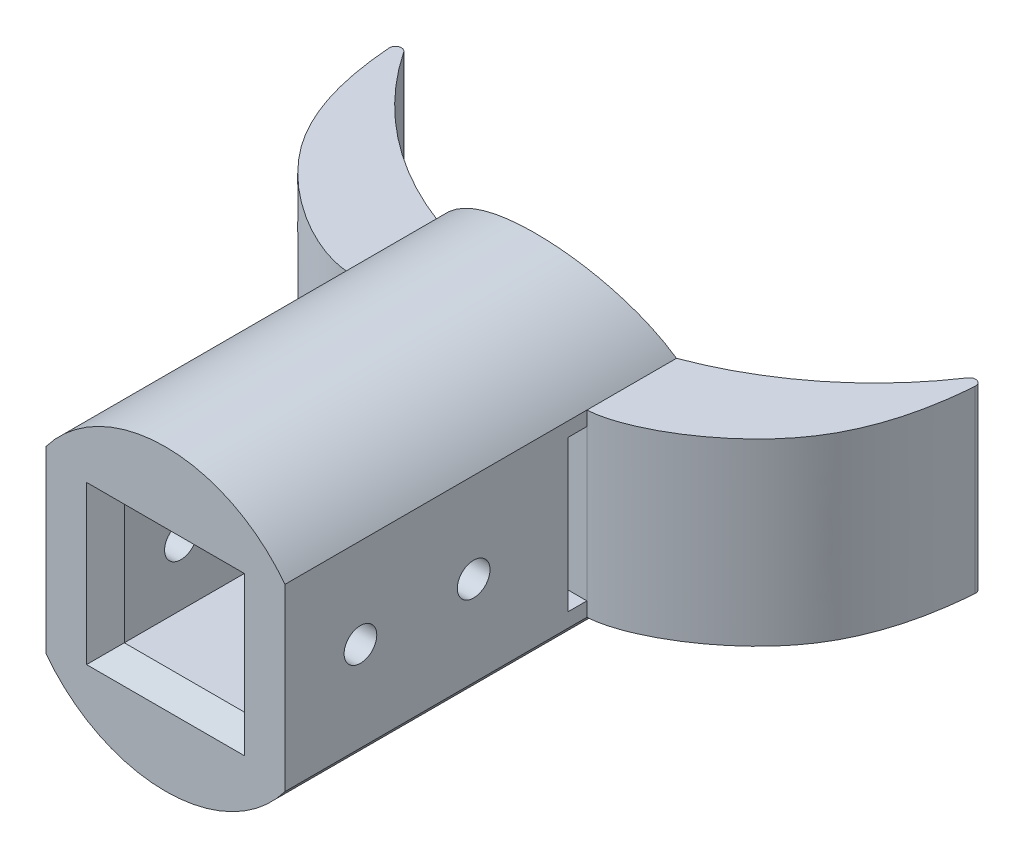
SolidWorks part; units mm, degrees
note: '?' marks a value the reader was unsure of.
ref_plane "前视" through (0, 0, 0) normal (0, 0, 1) x (1, 0, 0)
ref_plane "上视" through (0, 0, 0) normal (0, 1, 0) x (1, 0, 0)
ref_plane "右视" through (0, 0, 0) normal (1, 0, 0) x (0, 0, -1)
sketch "草图1" plane through (0, 0, 0) normal (0, 0, 1) x (1, 0, 0)
  line L1 (0, 0) -> (20.2, 0)
  line L2 (0, 0) -> (0, 20.2)
  line L3 (0, 20.2) -> (20.2, 20.2)
  line L4 (20.2, 0) -> (20.2, 20.2)
  line L5 (-10, -5) -> (30.2, -5)
  line L6 (-10, -5) -> (-10, 25.2)
  line L7 (-10, 25.2) -> (30.2, 25.2)
  line L8 (30.2, -5) -> (30.2, 25.2)
  dimension "D1" = 20.2
  dimension "D2" = 20.2
  dimension "D3" = 10
  dimension "D4" = 5
  dimension "D5" = 10
  dimension "D6" = 5
extrude "凸台-拉伸1" add sketch "草图1" along normal blind 50.8
sketch "草图2" plane through (0, -5, 0) normal (0, -1, 0) x (1, 0, 0)
  line L1 (-2.6, 9.3767) -> (22.8, 9.3767)
  line L2 (-2.6, 9.3767) -> (-2.6, 6.8367)
  line L3 (-2.6, 6.8367) -> (22.8, 6.8367)
  line L4 (22.8, 9.3767) -> (22.8, 6.8367)
  line L5 (10.1, 50.8) -> (10.1, 0) construction
  line L6 (-10, 50.8) -> (30.2, 50.8) construction
  line L7 (-10, 0) -> (30.2, 0) construction
  dimension "D1" = 2.54
  dimension "D2" = 25.4
  dimension "D3" = 12.7
sketch "草图3" plane through (0, 25.2, 0) normal (0, 1, 0) x (1, 0, 0)
  line L0 (30.2, 0) -> (-10, 0) construction
  line L1 (10.1, 68.58) -> (59.5934, 40.005) construction
  line L2 (10.1, 68.58) -> (-33.6794, 31.8447) construction
  line L3 (10.1, 68.58) -> (10.1, -10.7777) construction
  line L5 (-10, 0) -> (30.2, 0)
  arc A0 (-37.3657, 36.7503) -> (57.5657, 36.7503) centre (10.1, 68.58) ccw
  arc A1 (59.3935, 36.1192) -> (57.5657, 36.7503) centre (58.3963, 36.1934) ccw
  arc A2 (-37.3657, 36.7503) -> (-39.1935, 36.1192) centre (-38.1963, 36.1934) ccw
  spline S0 degree 3 poles (30.2, 0) (36.6831, 0.3779) (55.8803, 11.9878) (58.934, 29.946) (59.3935, 36.1192) knots 0 0 0 0 0.466383 0.846266 0.846266 0.846266 0.846266
  spline S1 degree 3 poles (-10, 0) (-16.4831, 0.3779) (-35.6803, 11.9878) (-38.734, 29.946) (-39.1935, 36.1192) knots 0 0 0 0 0.466383 0.846266 0.846266 0.846266 0.846266
  dimension "D1" = 57.15
  dimension "D5" = 1
  dimension "D2" = 68.58
  dimension "D3" = 60
  dimension "D4" = 50
extrude "凸台-拉伸2" add sketch "草图3" against normal blind 40.2 and the other way blind 10
sketch "草图4" plane through (-10, 0, 0) normal (-1, 0, 0) x (0, 0, 1)
  line L0 (0, 10.1) -> (50.8, 10.1) construction
  line L1 (0, 22.8) -> (3.2, 22.8)
  line L2 (0, 22.8) -> (0, -2.6)
  line L3 (0, -2.6) -> (3.2, -2.6)
  line L4 (3.2, 22.8) -> (3.2, -2.6)
  line L6 (50.8, 25.2) -> (50.8, -5) construction
  dimension "D1" = 25.4
  dimension "D2" = 12.7
  dimension "D3" = 3.2
  dimension "D4" = 50.8
extrude "切除-拉伸2" cut sketch "草图4" against normal through all
chamfer "倒角1" distance 3.175 angle 45 4 edges at (20.2, 10.1, 50.8) (10.1, 0, 50.8) (0, 10.1, 50.8) (10.1, 20.2, 50.8)
hole_wizard "M5 间隙孔1" positions "3D草图3" profile "草图11" hole size "M5" standard "GB" end condition through all
sketch3d "3D草图3"
  line L0 (30.2, 10.1, 50.8) -> (30.2, 10.1, -9.1804) construction
  line L1 (30.2, -5, 50.8) -> (30.2, 25.2, 50.8) construction
  point P0 (30.2, 10.1, 38.1)
  point P2 (30.2, 10.1, 19.05)
  dimension "D1" = 12.7
  dimension "D2" = 19.05
sketch "草图11" plane through (30.2, 10.1, 38.1) normal (0, 1, 0) x (0, 0, -1)
  line L0 (0, 0) -> (0, 69.3963)
  line L1 (0, 69.3963) -> (2.75, 69.3963)
  line L2 (2.75, 69.3963) -> (2.75, 0)
  line L5 (2.75, 0) -> (0, 0)
  line L11 (0, -6.35) -> (0, 107.95) construction
  dimension "通孔孔直径" = 5.5
  dimension "通孔孔深度" = 69.3963
sketch "草图12" plane through (0, 0, 50.8) normal (0, 0, 1) x (1, 0, 0)
  line L0 (30.2, 25.2) -> (-10, 25.2) construction
  line L1 (-10, 25.2) -> (30.2, 25.2)
  line L2 (-10, -5) -> (30.2, -5) construction
  line L5 (-10, -5) -> (30.2, -5)
  line L6 (-10, -5) -> (30.2, -5) construction
  arc A0 (-10, 25.2) -> (30.2, 25.2) centre (10.1, 9.9995) cw
  arc A1 (30.2, -5) -> (-10, -5) centre (10.1, 10.2005) cw
  point P4 (10.1, 35.2)
  point P5 (10.1, -15)
  dimension "D2" = 10
  dimension "D1" = 10
extrude "凸台-拉伸3" add sketch "草图12" against normal blind 50.8
sketch "草图14" plane through (0, 0, 50.8) normal (0, 0, 1) x (1, 0, 0)
  line L0 (-10, 35.2) -> (-53.4516, 35.2)
  line L1 (-53.4516, 35.2) -> (-53.4516, 25.2)
  line L2 (-10, 25.2) -> (-10, -5)
  line L3 (30.2, -5) -> (30.2, 25.2)
  line L4 (-10, 35.2) -> (-10, 25.2)
  line L5 (30.2, -5) -> (30.2, 25.2)
  line L6 (10.1, 35.2) -> (-10, 35.2)
  line L8 (10.1, 35.2) -> (-10, 35.2)
  line L9 (-53.4516, 25.2) -> (-10, 25.2)
  line L10 (10.1, 35.2) -> (10.1, -20.3662) construction
  line L11 (-10, 35.2) -> (-10, 25.2)
  line L12 (73.6516, 25.2) -> (30.2, 25.2)
  line L13 (30.2, 35.2) -> (73.6516, 35.2)
  line L14 (73.6516, 35.2) -> (73.6516, 25.2)
  line L15 (30.2, -15) -> (10.1, -15)
  line L16 (73.6516, -15) -> (73.6516, -5)
  line L17 (30.2, -15) -> (73.6516, -15)
  line L18 (73.6516, -5) -> (30.2, -5)
  line L19 (-10, -15) -> (-10, -5)
  line L20 (-53.4516, -5) -> (-10, -5)
  line L21 (10.1, -15) -> (-10, -15)
  line L22 (30.2, 35.2) -> (10.1, 35.2)
  line L23 (-53.4516, -15) -> (-53.4516, -5)
  line L24 (-40.1565, 10.1) -> (66.3517, 10.1) construction
  line L26 (-10, -15) -> (-53.4516, -15)
  arc A0 (30.2, -5) -> (-10, -5) centre (10.1, 10.2005) cw
  arc A1 (10.1, 35.2) -> (-10, 25.2) centre (10.1, 9.9995) ccw
  arc A2 (-10, -5) -> (30.2, -5) centre (10.1, 10.2005) ccw
  arc A3 (30.2, 25.2) -> (-10, 25.2) centre (10.1, 9.9995) ccw
  arc A4 (30.2, 25.2) -> (-10, 25.2) centre (10.1, 9.9995) ccw
  dimension "D1" = 0
  dimension "D2" = 0
ref_plane "基准面2" through (10.1, 0, 0) normal (-1, 0, 0) x (0, 0, 1)
ref_plane "基准面3" through (0, 10.1, 0) normal (0, 1, 0) x (1, 0, 0)
extrude "切除-拉伸3" cut sketch "草图14" against normal through all
ref_axis "基准轴1" through (10.1, 10.1, 0.9788) along (0, 0, 1)?
